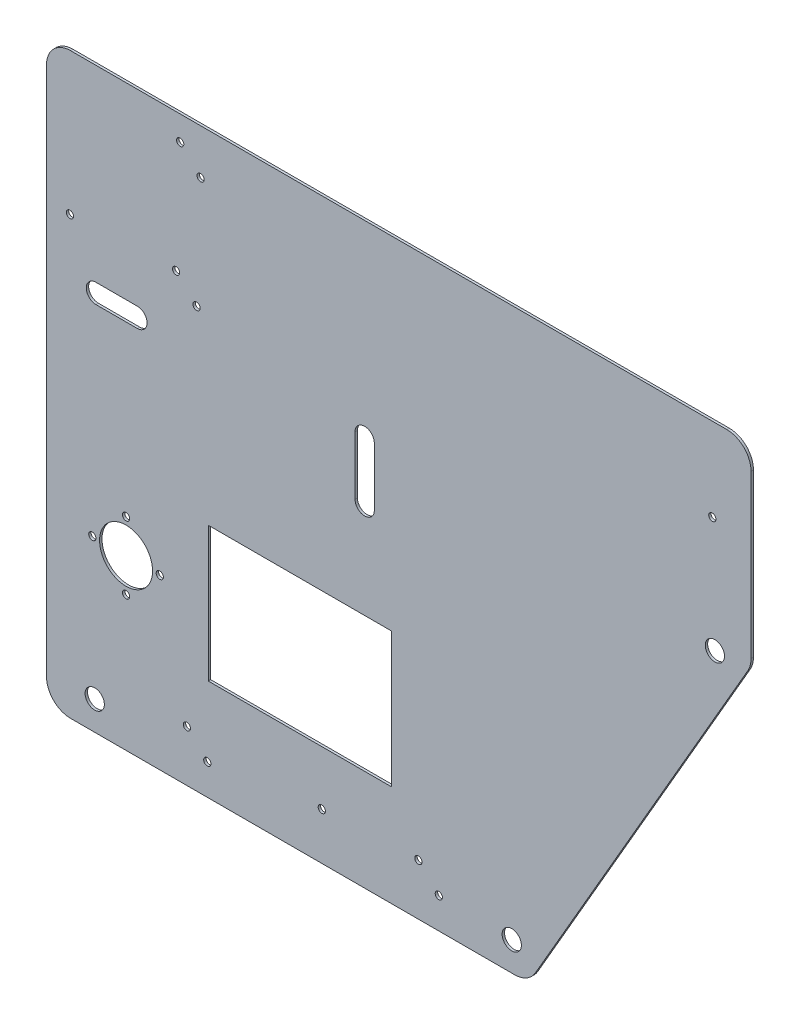
SolidWorks part; units mm, degrees
ref_plane "Front Plane" through (0, 0, 0) normal (0, 0, 1) x (1, 0, 0)
ref_plane "Top Plane" through (0, 0, 0) normal (0, 1, 0) x (1, 0, 0)
ref_plane "Right Plane" through (0, 0, 0) normal (1, 0, 0) x (0, 0, -1)
sketch "Sketch1" plane through (0, 0, 0) normal (0, 0, 1) x (1, 0, 0)
  line L0 (100, 80) -> (192.376, 80)
  line L1 (-100, -80) -> (100, -80)
  line L2 (-100, -80) -> (-100, 80)
  line L3 (-100, 80) -> (100, 80)
  line L4 (100, -80) -> (100, 80)
  line L5 (-100, -80) -> (100, 80) construction
  line L6 (-100, 80) -> (100, -80) construction
  line L7 (192.376, 80) -> (100, -80)
  line L8 (100, 80) -> (100, -80)
  line L10 (-100, 80) -> (192.376, 80)
  line L11 (-100, 80) -> (-100, 110)
  line L12 (-100, 110) -> (192.376, 110)
  line L13 (192.376, 80) -> (192.376, 110)
  point P0 (0, 0)
  dimension "D1" = 160
  dimension "D2" = 200
  dimension "D3" = 30
  dimension "D4" = 30
extrude "Boss-Extrude1" add sketch "Sketch1" along normal blind 1 contours L1 L4 L3 L2 | L7 L0 L4 | L11 L10 L13 L12 region at (0, 0, 0) region at (130.792, 26.6667, 0)
sketch "Sketch2" plane through (0, 0, 1) normal (0, 0, 1) x (1, 0, 0)
  line L0 (-100, -80) -> (100, -80) construction
  line L1 (192.376, 80) -> (100, -80) construction
  line L2 (-100, -80) -> (-100, 110) construction
  line L3 (-100, 110) -> (192.376, 110) construction
  line L4 (-79.5166, 78) -> (-62.3003, 78) construction
  line L7 (-100, -80) -> (-100, 110) construction
  line L8 (-29.8584, 15) -> (-29.8584, -35) construction
  line L9 (-79.5166, 82) -> (-62.3003, 82)
  line L10 (-79.5166, 74) -> (-62.3003, 74)
  line L11 (-32.8584, 18) -> (43.1416, 18)
  line L12 (-32.8584, 18) -> (-32.8584, -38)
  line L13 (-32.8584, -38) -> (43.1416, -38)
  line L14 (43.1416, 18) -> (43.1416, -38)
  line L15 (20.1416, 15) -> (-29.8584, 15) construction
  line L17 (40.1416, -35) -> (40.1416, 15) construction
  line L18 (32.0262, 82) -> (32.0262, 57.7776) construction
  line L19 (36.0262, 82) -> (36.0262, 57.7776)
  line L20 (28.0262, 82) -> (28.0262, 57.7776)
  circle A0 centre (93.0718, -68) radius 4
  circle A1 centre (177.3649, 78) radius 4
  circle A2 centre (-67, -10) radius 11
  circle A3 centre (-80, -68) radius 4
  circle A4 centre (-53, -10) radius 1.5
  circle A5 centre (-67, 4) radius 1.5
  circle A6 centre (-81, -10) radius 1.5
  circle A7 centre (-67, -24) radius 1.5
  circle A10 centre (32.0262, 70) radius 4 construction
  arc A11 (-79.5166, 82) -> (-79.5166, 74) centre (-79.5166, 78) ccw
  arc A12 (-62.3003, 74) -> (-62.3003, 82) centre (-62.3003, 78) ccw
  circle A32 centre (62.7961, -67.2426) radius 1.5
  circle A33 centre (54.3108, -58.7574) radius 1.5
  circle A34 centre (-33.2742, -67.2426) radius 1.5
  circle A35 centre (-41.7595, -58.7574) radius 1.5
  circle A36 centre (14.2259, -60.5) radius 1.5
  circle A37 centre (-37.7547, 94.2817) radius 1.5
  circle A38 centre (-46.24, 102.767) radius 1.5
  circle A39 centre (-90.2956, 101.0243) radius 1.5
  circle A40 centre (176.3056, 125.4889) radius 1.5
  arc A41 (36.0262, 82) -> (28.0262, 82) centre (32.0262, 82) ccw
  arc A42 (28.0262, 57.7776) -> (36.0262, 57.7776) centre (32.0262, 57.7776) ccw
  point P12 (-70.9085, 78)
  point P65 (32.0262, 69.8888)
  dimension "D3" = 8
  dimension "D4" = 8
  dimension "D9" = 22
  dimension "D10" = 8
  dimension "D12" = 3
  dimension "D13" = 3
  dimension "D14" = 3
  dimension "D15" = 3
  dimension "D16" = 14
  dimension "D20" = 4
  dimension "D22" = 8
  dimension "D23" = 3
  dimension "D24" = 20
  dimension "D25" = 3
  dimension "D1" = 12
  dimension "D2" = 12
  dimension "D5" = 32
  dimension "D6" = 12
  dimension "D7" = 33
  dimension "D8" = 70
  dimension "D11" = 12
  dimension "D17" = 14
  dimension "D18" = 14
  dimension "D19" = 14
  dimension "D21" = 40
  dimension "D26" = 3
  dimension "D27" = 3
  dimension "D28" = 8
  dimension "D29" = 3
extrude "Cut-Extrude1" cut sketch "Sketch2" against normal blind 3
sketch "Sketch3" plane through (0, 0, 1) normal (0, 0, 1) x (1, 0, 0)
  line L0 (192.376, 80) -> (192.376, 110) construction
  line L1 (-100, 110) -> (192.376, 110)
  line L2 (-100, 110) -> (-100, 160)
  line L3 (-100, 160) -> (192.376, 160)
  line L4 (192.376, 110) -> (192.376, 160)
  dimension "D1" = 50
extrude "Boss-Extrude2" add sketch "Sketch3" against normal blind 1
fillet "Fillet1" radius 10 5 edges at (100, -80, 0.5) (-100, -80, 0.5) (-100, 160, 0.5) (192.376, 160, 0.5) (192.376, 80, 0.5)
sketch "Sketch4" plane through (0, 0, 1) normal (0, 0, 1) x (1, 0, 0)
  circle A2 centre (-44.5363, 149.8294) radius 1.5
  circle A3 centre (-36.051, 141.3442) radius 1.5
  circle A4 centre (176.3056, 125.4889) radius 1.5
  dimension "D1" = 3
extrude "Cut-Extrude2" cut sketch "Sketch4" against normal blind 11
